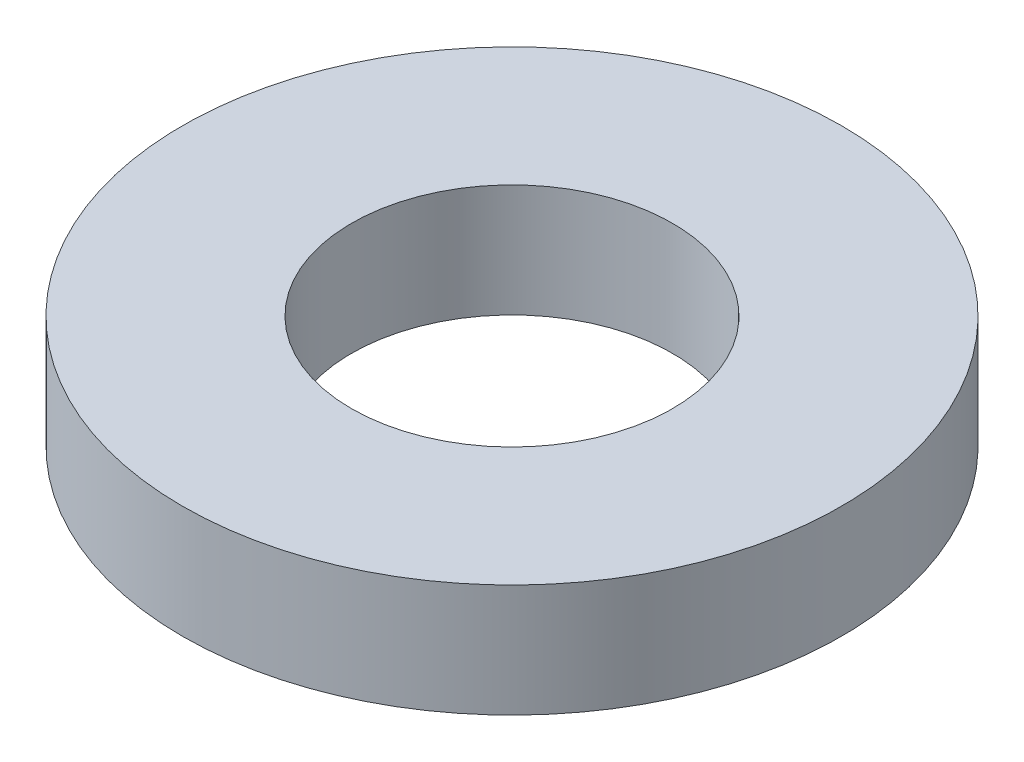
SolidWorks part; units mm, degrees
ref_plane "Front Plane" through (0, 0, 0) normal (0, 0, 1) x (1, 0, 0)
ref_plane "Top Plane" through (0, 0, 0) normal (0, 1, 0) x (1, 0, 0)
ref_plane "Right Plane" through (0, 0, 0) normal (1, 0, 0) x (0, 0, -1)
sketch "Sketch1" plane through (0, 0, 0) normal (0, 1, 0) x (1, 0, 0)
  circle A0 centre (0, 0) radius 2.85
  circle A1 centre (0, 0) radius 5.85
  dimension "D1" = 5.7
  dimension "D2" = 3
extrude "Boss-Extrude1" add sketch "Sketch1" along normal blind 2
